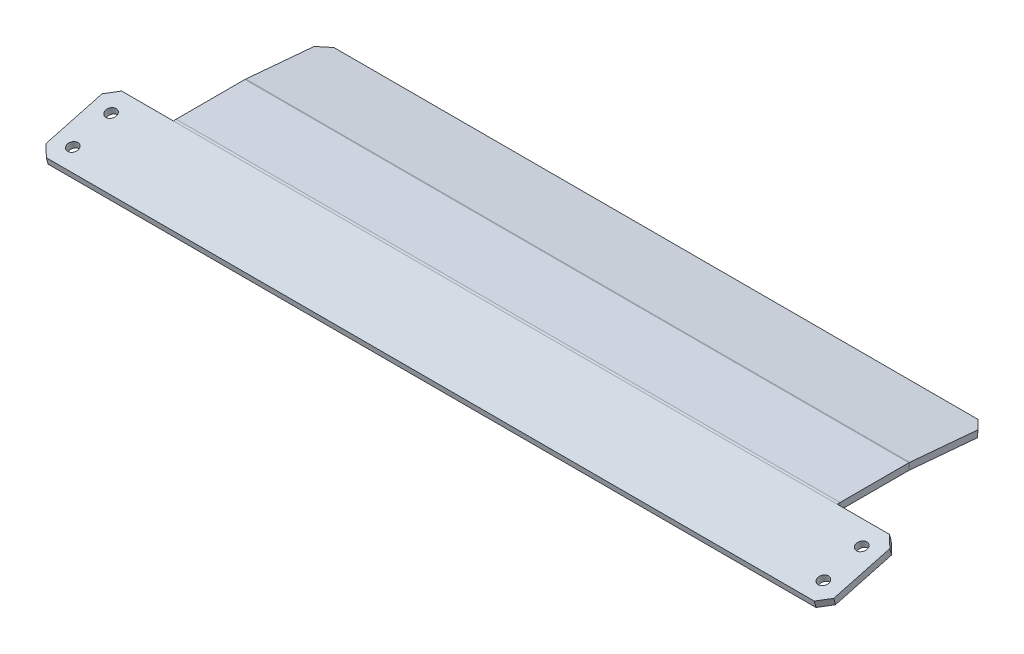
SolidWorks part; units mm, degrees
note: The reader was unsure of these and kept them because the rebuilt part matched: thickness of "Base-Flange1", "Edge-Flange1", "Edge-Flange2", "Sheet-Metal1", "Sheet-Metal2", "Sheet-Metal3", "Sheet-Metal4"; flange length of "Edge-Flange1", "Edge-Flange2".
ref_plane "Front Plane" through (0, 0, 0) normal (0, 0, 1) x (1, 0, 0)
ref_plane "Top Plane" through (0, 0, 0) normal (0, 1, 0) x (1, 0, 0)
ref_plane "Right Plane" through (0, 0, 0) normal (1, 0, 0) x (0, 0, -1)
sketch "Sketch1" plane through (0, 0, 0) normal (0, 1, 0) x (1, 0, 0)
  line L1 (212.725, -22.225) -> (-212.725, -22.225)
  line L3 (212.725, 22.225) -> (-212.725, 22.225)
  line L5 (212.725, -22.225) -> (-212.725, 22.225) construction
  line L6 (212.725, 22.225) -> (-212.725, -22.225) construction
  line L8 (-212.725, 22.225) -> (-212.725, -22.225)
  line L10 (212.725, 22.225) -> (212.725, -22.225)
  point P0 (0, 0)
  dimension "D1" = 425.45
  dimension "D2" = 44.45
base flange "Base-Flange1" sketch "Sketch1" thickness 4.2672 reverse thickness direction no parameters "D1"=2.032
edge flange "Edge-Flange1" sketch "Sketch8" flange angle 165 flange length 50.7348 flange position material outside bend radius 2.032 thickness 4.2672 relief rectangular parameters "D6"=10
sketch "Sketch8" plane through (0, -4.2672, 22.225) normal (0, 0.9659, 0.2588) x (-1, 0, 0)
  line L3 (-252.4125, 50.173) -> (252.4125, 50.173)
  line L11 (212.725, 0) -> (-212.725, 0) construction
  line L12 (252.4125, 0) -> (-252.4125, 0)
  line L13 (252.4125, 0) -> (252.4125, 50.173)
  line L14 (-252.4125, 0) -> (-252.4125, 50.173)
  line L15 (-212.725, -44.0398) -> (212.725, -44.0398) construction
  point P4 (0, -44.0398)
  dimension "D1" = 252.4125
  dimension "D2" = 504.825
  dimension "D3" = 50.173
bend "EdgeBend1" bend radius 2.032 bend angle 15 parameters "D5"=1
edge flange "Edge-Flange2" sketch "Sketch11" flange angle 175 flange length 50.5696 flange position material outside bend radius 2.032 thickness 4.2672 relief rectangular parameters "D6"=10
sketch "Sketch11" plane through (0, -4.2672, -22.225) normal (0, 0.9962, -0.0872) x (1, 0, 0)
  line L3 (-212.725, 50.3833) -> (212.725, 50.3833)
  line L15 (212.725, 0) -> (-212.725, 0) construction
  line L16 (212.725, 0) -> (-212.725, 0)
  line L17 (-212.725, 50.3833) -> (-212.725, 0)
  line L18 (212.725, 50.3833) -> (212.725, 0)
  line L20 (-212.725, -0.3719) -> (-212.725, -44.3863) construction
  line L21 (212.725, -44.3863) -> (212.725, -0.3719) construction
  dimension "D3" = 50.3833
bend "EdgeBend2" bend radius 2.032 bend angle 5 parameters "D5"=2
chamfer "Chamfer1" distance 6.35 angle 45 6 edges at (-252.4125, -15.192, 71.2406) (-252.4125, -2.2755, 23.0356) (-212.725, -6.5329, -72.6026) (212.725, -6.5329, -72.6026) (252.4125, -2.2755, 23.0356) (252.4125, -15.192, 71.2406)
hole_wizard "17/64 (0.26563) Diameter Hole1" positions "Sketch12" profile "Sketch13" hole size "17/64" standard "ANSI Inch" end condition through all
sketch "Sketch12" plane through (0, 5.6967, 1.5264) normal (0, 0.9659, 0.2588) x (1, 0, 0)
  line L0 (-246.0625, -22.8397) -> (-212.725, -22.8397) construction
  point P0 (-240.5062, -35.5397)
  point P2 (-240.5062, -60.9397)
  point P4 (240.5062, -60.9397)
  point P6 (240.5062, -35.5397)
  dimension "D1" = 25.4
  dimension "D2" = 12.7
  dimension "D3" = 240.5062
  dimension "D4" = 240.5062
sketch "Sketch13" plane through (-240.5062, -3.5016, 35.8551) normal (1, 0, 0) x (0, -0.2588, 0.9659)
  line L0 (0, 0) -> (0, 41.4018)
  line L1 (0, 41.4018) -> (3.3735, 41.4018)
  line L2 (3.3735, 41.4018) -> (3.3735, 0)
  line L5 (3.3735, 0) -> (0, 0)
  line L11 (0, -6.35) -> (0, 107.95) construction
  dimension "Thru Hole Dia." = 6.747
  dimension "Thru Hole Depth" = 41.4018
sketch "Bend-Lines1" [suppressed] plane through (0, 0, 0) normal (0, 1, 0) x (1, 0, 0)
sketch "Bounding-Box1" [suppressed] plane through (0, 0, 0) normal (0, 1, 0) x (1, 0, 0)
sheet metal parameters "Sheet-Metal1" thickness 4.2672 parameters "D1"=2.032, "D7"=4.7625
flat pattern "Flat-Pattern1" [suppressed]
sketch "Bend-Lines2" plane through (0, 0, 0) normal (0, 1, 0) x (1, 0, 0)
sketch3d "Bounding-Box2" [suppressed]
  line L0 (477.8375, -22.225, 0) -> (7.9375, -22.225, 0) construction
  line L1 (477.8375, 22.225, 0) -> (7.9375, 22.225, 0) construction
  line L2 (477.8375, -22.225, 0) -> (477.8375, 22.225, 0) construction
  line L3 (7.9375, -22.225, 0) -> (7.9375, 22.225, 0) construction
sheet metal parameters "Sheet-Metal2" thickness 4.2672 parameters "D1"=2.032, "D7"=4.7625
flat pattern "Flat-Pattern1"
sketch "Bend-Lines2" plane through (0, 0, 0) normal (0, 1, 0) x (1, 0, 0)
  line L0 (-234.95, -22.5352) -> (234.95, -22.5352) construction
  line L1 (-234.95, -22.5352) -> (234.95, -22.5352) construction
sketch3d "Bounding-Box2" [suppressed]
  line L0 (477.8375, -73.0184, 0) -> (7.9375, -73.0184, 0) construction
  line L1 (477.8375, 22.225, 0) -> (7.9375, 22.225, 0) construction
  line L2 (477.8375, -73.0184, 0) -> (477.8375, 22.225, 0) construction
  line L3 (7.9375, -73.0184, 0) -> (7.9375, 22.225, 0) construction
bend of the flat pattern "Flatten-<EdgeBend1>1"
sheet metal parameters "Sheet-Metal3" thickness 4.2672 parameters "D1"=2.032, "D7"=4.7625
flat pattern "Flat-Pattern1"
sketch "Bend-Lines2" plane through (0, 0, 0) normal (0, 1, 0) x (1, 0, 0)
  line L0 (-236.5375, -22.5352) -> (236.5375, -22.5352) construction
  line L1 (-236.5375, -22.5352) -> (236.5375, -22.5352) construction
  line L2 (236.5375, 22.4324) -> (-236.5375, 22.4324) construction
  line L3 (236.5375, 22.4324) -> (-236.5375, 22.4324) construction
sketch3d "Bounding-Box2" [suppressed]
  line L0 (266.7, 73.023, 0) -> (-266.7, 73.023, 0) construction
  line L1 (266.7, -73.0184, 0) -> (-266.7, -73.0184, 0) construction
  line L2 (266.7, 73.023, 0) -> (266.7, -73.0184, 0) construction
  line L3 (-266.7, 73.023, 0) -> (-266.7, -73.0184, 0) construction
bend of the flat pattern "Flatten-<EdgeBend1>1"
bend of the flat pattern "Flatten-<EdgeBend2>1"
sheet metal parameters "Sheet-Metal4" thickness 4.2672 parameters "D1"=2.032, "D7"=4.7625
flat pattern "Flat-Pattern1"
sketch "Bend-Lines2" plane through (0, 0, 0) normal (0, 1, 0) x (1, 0, 0)
  line L0 (-212.725, -22.5028) -> (212.725, -22.5028) construction
  line L1 (-212.725, -22.5028) -> (212.725, -22.5028) construction
  line L2 (212.725, 22.318) -> (-212.725, 22.318) construction
  line L3 (212.725, 22.318) -> (-212.725, 22.318) construction
sketch3d "Bounding-Box2" [suppressed]
  line L0 (252.4125, 72.7944, 0) -> (-252.4125, 72.7944, 0) construction
  line L1 (252.4125, -72.9535, 0) -> (-252.4125, -72.9535, 0) construction
  line L2 (252.4125, 72.7944, 0) -> (252.4125, -72.9535, 0) construction
  line L3 (-252.4125, 72.7944, 0) -> (-252.4125, -72.9535, 0) construction
bend of the flat pattern "Flatten-<EdgeBend1>1"
bend of the flat pattern "Flatten-<EdgeBend2>1"
